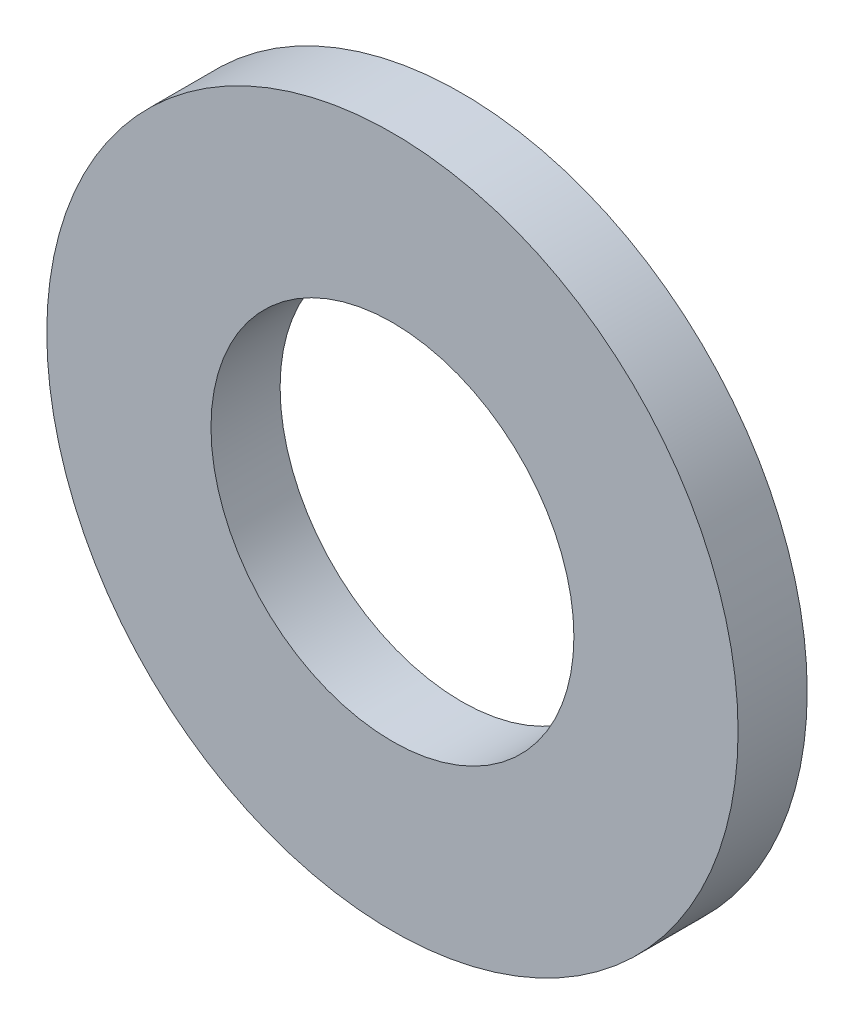
SolidWorks part; units mm, degrees
ref_plane "Plane1" through (0, 0, 0) normal (0, 0, 1) x (1, 0, 0)
ref_plane "Plane2" through (0, 0, 0) normal (0, 1, 0) x (1, 0, 0)
ref_plane "Plane3" through (0, 0, 0) normal (1, 0, 0) x (0, 0, -1)
sketch "Sketch1" plane through (0, 0, 0) normal (0, 0, 1) x (1, 0, 0)
  circle A0 centre (0, 0) radius 5.25
  circle A1 centre (0, 0) radius 10
  dimension "d1 Huldiameter" = 10.5
  dimension "d2 Udv.diameter" = 20
extrude "Base-Extrude" add sketch "Sketch1" along normal blind 2
sketch "Sketch2" [suppressed] plane through (0, 0, 1) normal (0, 0, 1) x (1, 0, 0)
  circle A0 centre (0, 15) radius 1.5
  dimension "D1" = 3
  dimension "D2" = 15
extrude "Cut-Extrude1" [suppressed] cut sketch "Sketch2" against normal through all
sketch "Sketch3" [suppressed] plane through (0, 0, 1) normal (0, 0, 1) x (1, 0, 0)
  circle A0 centre (0, 0) radius 19 construction
  circle A1 centre (0, 15) radius 1.5 construction
  circle A2 centre (0, 0) radius 11 construction
  circle A3 centre (0, 0) radius 19
  circle A4 centre (0, 15) radius 1.5
  circle A5 centre (0, 0) radius 11
extrude "Boss-Extrude3" [suppressed] add sketch "Sketch3" along normal blind 0.5
sketch "Sketch4" plane through (0, 0, 0) normal (0, 0, 1) x (1, 0, 0)
  line L0 (-2.5, -12.2474) -> (-2.5, -10.5)
  line L1 (-2.5, -10.5) -> (2.5, -10.5)
  line L2 (2.5, -10.5) -> (2.5, -12.2474)
  line L3 (0, 0) -> (0, -17.8897) construction
  arc A0 (2.5, -12.2474) -> (-2.5, -12.2474) centre (0, 0) ccw
  circle A1 centre (0, 0) radius 16
  dimension "d" = 25
  dimension "d1" = 32
  dimension "f" = 5
  dimension "M" = 23
extrude "Extrude1" [suppressed] add sketch "Sketch4" along normal blind 1.25
sketch "Sketch5" [suppressed] plane through (0, 0, 0) normal (1, 0, 0) x (0, 0, -1)
  line L0 (0, -30.5) -> (0, -33.9729)
  line L1 (0, -33.5) -> (0, 33.5) construction
  line L2 (-0.1808, -34.5465) -> (-4.3495, -40.5)
  line L3 (-4.3495, -40.5) -> (-5.5782, -39.6396)
  line L4 (-5.5782, -39.6396) -> (-1.6808, -34.0736)
  line L5 (-1.5, -33.5) -> (-1.5, -30.5)
  line L6 (-1.5, -30.5) -> (0, -30.5)
  line L7 (-1.5, 33.5) -> (-1.5, -33.5) construction
  line L8 (0, 0) -> (-4.0582, 0) construction
  line L9 (-1.5, -33.5) -> (0, -33.5) construction
  arc A0 (-1.6808, -34.0736) -> (-1.5, -33.5) centre (-2.5, -33.5) ccw
  arc A1 (0, -33.9729) -> (-0.1808, -34.5465) centre (-1, -33.9729) cw
  dimension "D3" = 1
  dimension "d2" = 42
  dimension "D4" = 3
  dimension "D5" = 35
extrude "Extrude2" [suppressed] add sketch "Sketch5" along normal mid plane 5
pattern_circular "CirPattern1" [suppressed] count 13 over 360 of bodies 108
sketch "Sketch6" [suppressed] plane through (0, 0, 2.34) normal (0, 0, 1) x (1, 0, 0)
  line L0 (0, 7.5) -> (0, 14.1) construction
  line L1 (-1, 10.8) -> (-1, 7.433)
  line L2 (1, 10.8) -> (1, 7.433)
  circle A1 centre (0, 0) radius 7.5 construction
  circle A2 centre (0, 0) radius 14.1 construction
  arc A3 (1, 10.8) -> (-1, 10.8) centre (0, 10.8) ccw
  arc A4 (1, 7.433) -> (-1, 7.433) centre (0, 0) ccw
  point P9 (0, 10.8)
  dimension "D1" = 1
extrude "Cut-Extrude2" [suppressed] cut sketch "Sketch6" against normal through all
pattern_circular "CirPattern2" [suppressed] count 6 over 360
